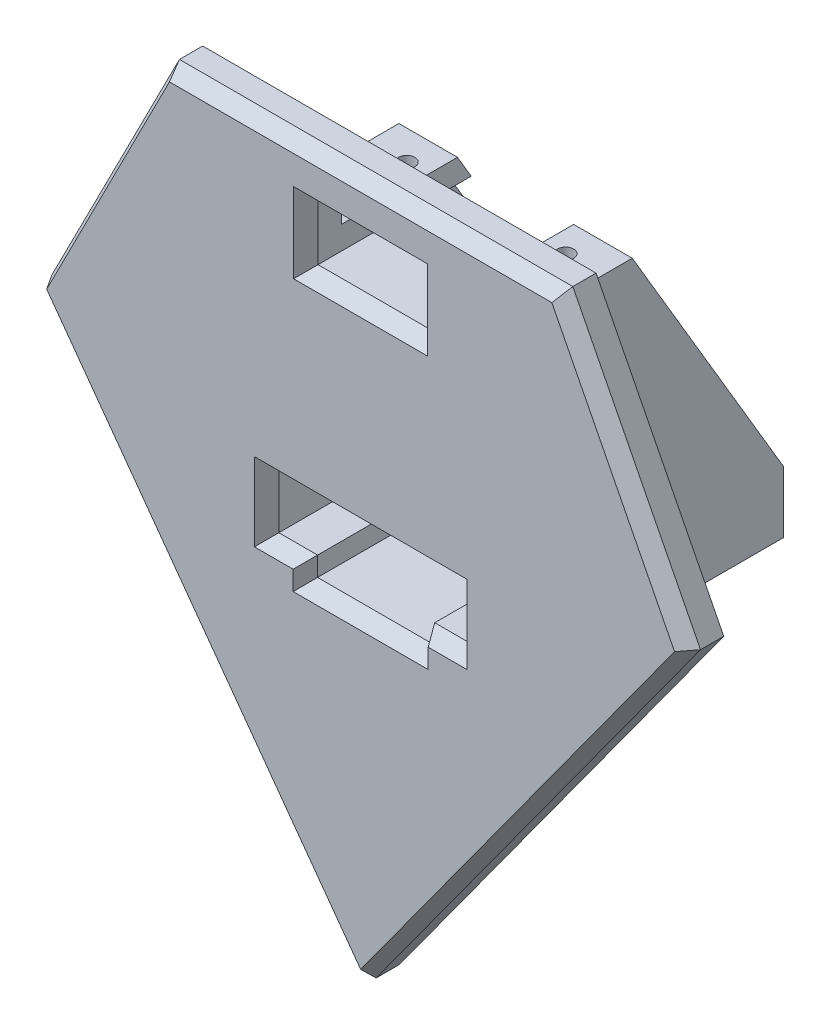
SolidWorks part; units mm, degrees
ref_plane "Front Plane" through (0, 0, 0) normal (0, 0, 1) x (1, 0, 0)
ref_plane "Top Plane" through (0, 0, 0) normal (0, 1, 0) x (1, 0, 0)
ref_plane "Right Plane" through (0, 0, 0) normal (1, 0, 0) x (0, 0, -1)
sketch "Sketch2" plane through (0, 0, 0) normal (0, 1, 0) x (1, 0, 0)
  line L0 (15.061, 0) -> (15.061, 32)
  line L1 (-12.561, 2.5) -> (12.561, 2.5)
  line L2 (-12.561, 2.5) -> (-12.561, 32)
  line L4 (12.561, 2.5) -> (12.561, 32)
  line L5 (15.061, 32) -> (12.561, 32)
  line L7 (-15.061, 32) -> (-15.061, 0)
  line L8 (-15.061, 0) -> (15.061, 0)
  line L10 (-15.061, 32) -> (-12.561, 32)
  point P4 (0, 2.5)
  point P12 (0, 0)
  dimension "D1" = 2.5
  dimension "D2" = 2.5
  dimension "D3" = 29.5
  dimension "D4" = 25.122
extrude "Boss-Extrude1" add sketch "Sketch2" along normal blind 32.5
sketch "Sketch4" plane through (0, 0, 0) normal (0, -1, 0) x (1, 0, 0)
  line L10 (-7.561, -6) -> (-7.561, 0)
  line L13 (-12.561, -2.5) -> (-12.561, -32) construction
  line L18 (-12.561, -10) -> (-7.561, -6)
  line L23 (12.561, -32) -> (12.561, -2.5) construction
  line L26 (12.561, -10) -> (7.561, -6)
  line L33 (-15.061, -32) -> (-15.061, 0) construction
  line L36 (15.061, 0) -> (15.061, -32) construction
  line L38 (-7.561, 0) -> (-15.061, 0)
  line L39 (7.561, -6) -> (7.561, 0)
  line L40 (7.561, 0) -> (15.061, 0)
  line L41 (-15.061, 0) -> (-15.061, -32)
  line L42 (-15.061, -32) -> (-12.561, -32)
  line L43 (-12.561, -32) -> (-15.061, -32) construction
  line L44 (-12.561, -32) -> (-12.561, -10)
  line L45 (12.561, -10) -> (12.561, -32)
  line L46 (12.561, -32) -> (15.061, -32)
  line L47 (15.061, -32) -> (15.061, 0)
  circle A2 centre (-10.2499, -4.95) radius 1.05
  circle A5 centre (10.2499, -4.95) radius 1.05
  dimension "D4" = 6
  dimension "D5" = 2.1
  dimension "D1" = 7.5
  dimension "D2" = 7.5
  dimension "D3" = 10
extrude "Boss-Extrude2" add sketch "Sketch4" along normal blind 2.5
sketch "Sketch5" plane through (0, 32.5, 0) normal (0, 1, 0) x (1, 0, 0)
  line L0 (-15.061, 32) -> (-10.2499, 32)
  line L9 (-10.2499, 32) -> (-6.25, 26)
  line L13 (-15.061, 0) -> (15.061, 0) construction
  line L14 (15.061, 0) -> (-15.061, 0)
  line L15 (-15.061, 0) -> (-15.061, 32)
  line L20 (15.061, 0) -> (15.061, 32)
  line L21 (-6.25, 26) -> (6.25, 26)
  line L22 (6.25, 26) -> (10.2499, 32)
  line L23 (10.2499, 32) -> (15.061, 32)
  circle A0 centre (-10.2499, 4.95) radius 1.05 construction
  circle A1 centre (-10.2499, 8.7) radius 1.05
  circle A2 centre (10.2499, 8.7) radius 1.05
  point P6 (0, 26)
  dimension "D4" = 0
  dimension "D1" = 8.7
  dimension "D2" = 12.5
  dimension "D3" = 20.4998
  dimension "D5" = 6
extrude "Boss-Extrude3" add sketch "Sketch5" along normal blind 3
sketch "Sketch6" plane through (-15.061, 0, 0) normal (-1, 0, 0) x (0, 0, 1)
  line L0 (-12.5, 35.5) -> (-32, 2.5)
  line L1 (-32, 2.5) -> (-32, 35.5)
  line L2 (-32, 35.5) -> (-12.5, 35.5)
  line L3 (-32, 35.5) -> (-32, -2.5) construction
  line L4 (-32, 35.5) -> (0, 35.5) construction
  line L6 (0, -2.5) -> (-32, -2.5) construction
  line L7 (0, 35.5) -> (0, -2.5) construction
  dimension "D1" = 5
  dimension "D2" = 12.5
extrude "Cut-Extrude1" cut sketch "Sketch6" against normal through all
ref_plane "Plane1" through (0, 16.5, 0) normal (0, -1, 0) x (-1, 0, 0)
sketch "Sketch13" plane through (0, 0, 0) normal (0, 0, 1) x (1, 0, 0)
  line L1 (-15.061, 35.5) -> (15.061, 35.5)
  line L2 (-15.061, 35.5) -> (-15.061, -2.5)
  line L3 (-15.061, -2.5) -> (15.061, -2.5)
  line L4 (15.061, 35.5) -> (15.061, -2.5)
extrude "Boss-Extrude7" add sketch "Sketch13" along normal blind 2.5
sketch "Sketch8" plane through (0, 0, 2.5) normal (0, 0, 1) x (1, 0, 0)
  line L0 (0, -43.5) -> (-43.5926, 16.5)
  line L1 (-16.5671, 16.5) -> (16.5671, 16.5) construction
  line L2 (-43.5926, 16.5) -> (43.5926, 16.5)
  line L3 (43.5926, 16.5) -> (0, -43.5)
  dimension "D1" = 72
  dimension "D2" = 60
extrude "Boss-Extrude4" add sketch "Sketch8" along normal blind 5
sketch "Sketch9" plane through (0, 0, 2.5) normal (0, 0, 1) x (1, 0, 0)
  line L0 (43.5926, 16.5) -> (65.3888, 46.5)
  line L1 (65.3888, 46.5) -> (-65.3888, 46.5)
  line L2 (-65.3888, 46.5) -> (-43.5926, 16.5)
  line L3 (43.5926, 16.5) -> (-43.5926, 16.5)
  line L4 (0, -43.5) -> (43.5926, 16.5) construction
  line L5 (-43.5926, 16.5) -> (0, -43.5) construction
  dimension "D1" = 30
extrude "Boss-Extrude6" add sketch "Sketch9" along normal up to surface (5 mm away) up to face at (0, -3.5, 7.5)
sketch "Sketch10" plane through (0, 0, 2.5) normal (0, 0, -1) x (-1, 0, 0)
  line L25 (-25.3888, 46.5) -> (-65.3888, 46.5)
  line L26 (-65.3888, 46.5) -> (65.3888, 46.5) construction
  line L27 (-65.3888, 46.5) -> (-41.8774, 14.1393)
  line L28 (0, -43.5) -> (-65.3888, 46.5) construction
  line L29 (-41.8774, 14.1393) -> (-25.3888, 46.5)
  line L30 (65.3888, 46.5) -> (41.8774, 14.1393)
  line L31 (65.3888, 46.5) -> (0, -43.5) construction
  line L32 (41.8774, 14.1393) -> (25.3888, 46.5)
  line L33 (25.3888, 46.5) -> (65.3888, 46.5)
  dimension "D1" = 40
extrude "Cut-Extrude2" cut sketch "Sketch10" against normal through all
sketch "Sketch14" plane through (0, 0, -2.5) normal (0, 0, -1) x (-1, 0, 0)
  line L11 (-7.561, -2.5) -> (7.561, -2.5)
  line L12 (15.061, -2.5) -> (-15.061, -2.5) construction
  line L13 (7.561, -2.5) -> (7.561, 0)
  line L14 (12.561, 0) -> (7.561, 0) construction
  line L15 (7.561, -2.5) -> (7.561, 0) construction
  line L16 (7.561, 0) -> (12.561, 0)
  line L17 (12.561, 0) -> (12.561, 7.7837)
  line L18 (12.561, 2.5) -> (12.561, 32.5) construction
  line L19 (12.561, 7.7837) -> (-12.561, 7.7837)
  line L20 (-12.561, 32.5) -> (-12.561, 2.5) construction
  line L21 (-12.561, 7.7837) -> (-12.561, 0)
  line L22 (-12.561, 2.5) -> (-12.561, -2.5) construction
  line L23 (-7.561, 0) -> (-12.561, 0) construction
  line L24 (-12.561, 0) -> (-7.561, 0)
  line L25 (-7.561, 0) -> (-7.561, -2.5)
  line L26 (-7.561, -2.5) -> (-12.561, -2.5) construction
  line L27 (-15.061, 35.5) -> (15.061, 35.5) construction
  line L28 (-7.5, 35.5) -> (7.5, 35.5)
  line L29 (-7.5, 35.5) -> (-7.5, 40.5)
  line L30 (-7.5, 40.5) -> (7.5, 40.5)
  line L31 (7.5, 35.5) -> (7.5, 40.5)
  point P37 (0, 35.5)
  dimension "D1" = 15
  dimension "D2" = 5
extrude "Cut-Extrude3" cut sketch "Sketch14" against normal through all
sketch "Sketch15" plane through (0, -2.5, 0) normal (0, -1, 0) x (1, 0, 0)
  line L1 (15.061, -32) -> (-15.061, -32)
  line L2 (15.061, -32) -> (15.061, 2.5)
  line L3 (15.061, 2.5) -> (-15.061, 2.5)
  line L4 (-15.061, -32) -> (-15.061, 2.5)
  circle A0 centre (-10.2499, -4.95) radius 2.495
  circle A1 centre (10.341, -4.95) radius 2.495
  dimension "D1" = 4.99
  dimension "D2" = 4.99
extrude "Boss-Extrude8" add sketch "Sketch15" along normal blind 3
sketch "Sketch17" plane through (0, -5.5, 0) normal (0, -1, 0) x (1, 0, 0)
  line L0 (15.061, 2.5) -> (-15.061, 2.5) construction
  circle A0 centre (0, -37.5) radius 13.75
  dimension "D2" = 27.5
  dimension "D1" = 40
extrude "Cut-Extrude4" cut sketch "Sketch17" against normal through all
sketch "Sketch19" plane through (0, 0, -2.5) normal (0, 0, -1) x (-1, 0, 0)
  line L0 (-15.061, 35.5) -> (15.061, 35.5) construction
  line L1 (7.5, 35.5) -> (-7.5, 35.5)
  line L2 (7.5, 35.5) -> (7.5, 32.5)
  line L3 (7.5, 32.5) -> (-7.5, 32.5)
  line L4 (-7.5, 35.5) -> (-7.5, 32.5)
  line L5 (7.5, 35.5) -> (7.5, 40.5) construction
  line L6 (-7.5, 40.5) -> (-7.5, 35.5) construction
  line L7 (-12.561, 32.5) -> (12.561, 32.5) construction
  dimension "D1" = 0
  dimension "D2" = 0
  dimension "D3" = 0
extrude "Cut-Extrude6" cut sketch "Sketch19" along normal through all both and the other way through all
chamfer "Chamfer1" distance 2 angle 30 17 edges at (-20.9387, -14.6803, 7.5) (-33.6331, 30.3197, 7.5) (0, 46.5, 7.5) (33.6331, 30.3197, 7.5) (20.9387, -14.6803, 7.5) (7.5, 36.5, 7.5) (0, 40.5, 7.5) (-7.5, 36.5, 7.5) (0, 32.5, 7.5) (12.561, 3.8918, 7.5) (0, 7.7837, 7.5) (-12.561, 3.8918, 7.5) (-10.061, 0, 7.5) (-7.561, -1.25, 7.5) (0, -2.5, 7.5) (7.561, -1.25, 7.5) (10.061, 0, 7.5) first distance on face at (-20.9387, -14.6803, 5) first distance on face at (-33.6331, 30.3197, 5) first distance on face at (0, 46.5, 5) first distance on face at (33.6331, 30.3197, 5) first distance on face at (20.9387, -14.6803, 5) first distance on face at (7.5, 35.6429, -1.3247) first distance on face at (0, 40.5, 5) first distance on face at (-7.5, 35.6429, -1.3247) first distance on face at (0, 32.5, 2.5) first distance on face at (12.561, 8.6917, -9.7874) first distance on face at (0, 7.7837, 2.5) first distance on face at (-12.561, 8.6917, -9.7874) first distance on face at (-10.061, 0, -0.25) first distance on face at (-7.561, -1.25, 0.75) first distance on face at (0, -2.5, -9.0821) first distance on face at (7.561, -1.25, 0.75) first distance on face at (10.061, 0, -0.25)
